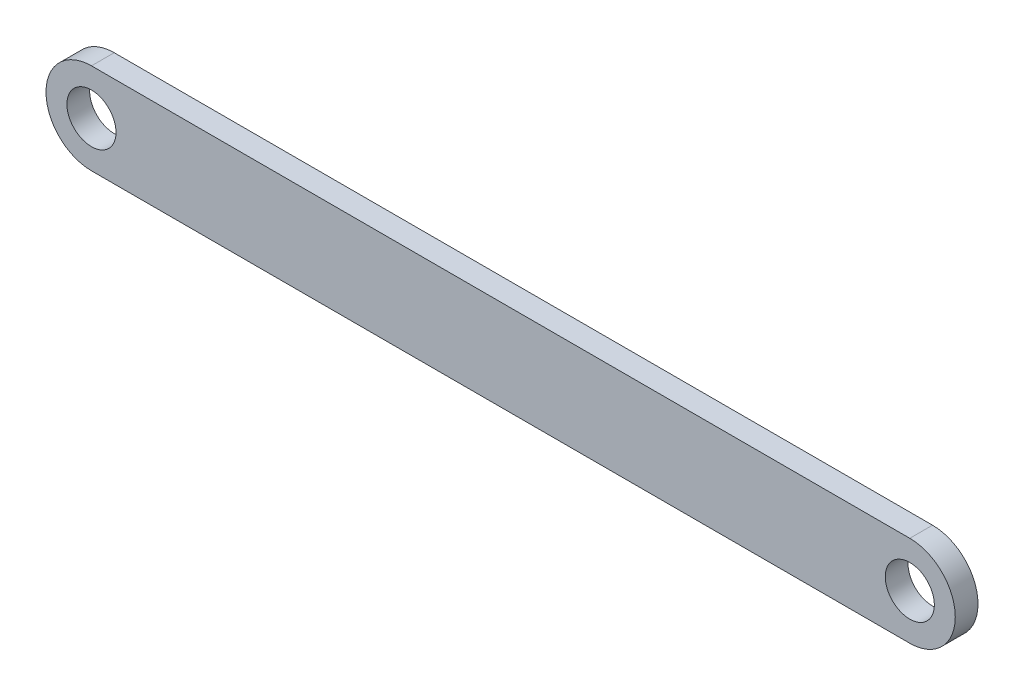
SolidWorks part; units mm, degrees
ref_plane "Front Plane" through (0, 0, 0) normal (0, 0, 1) x (1, 0, 0)
ref_plane "Top Plane" through (0, 0, 0) normal (0, 1, 0) x (1, 0, 0)
ref_plane "Right Plane" through (0, 0, 0) normal (1, 0, 0) x (0, 0, -1)
sketch "Sketch1" plane through (0, 0, 0) normal (0, 0, 1) x (1, 0, 0)
  line L1 (0, 0) -> (200, 0)
  line L2 (0, 0) -> (0, 20)
  line L3 (0, 20) -> (200, 20)
  line L4 (200, 0) -> (200, 20)
extrude "Boss-Extrude1" add sketch "Sketch1" along normal blind 5
fillet "Fillet1" 2 edges at (200, 20, 2.5) (200, 0, 2.5) type full round first side face at (100, 20, 2.5) second side face at (100, 0, 2.5) middle face at (200, 10, 2.5)
fillet "Fillet2" 2 edges at (0, 20, 2.5) (0, 0, 2.5) type full round first side face at (95, 20, 2.5) second side face at (95, 0, 2.5) middle face at (0, 10, 2.5)
sketch "Sketch2" plane through (0, 0, 5) normal (0, 0, 1) x (1, 0, 0)
  circle A0 centre (10, 10) radius 5.4
  circle A1 centre (190, 10) radius 5.4
extrude "Cut-Extrude1" cut sketch "Sketch2" against normal blind 5
